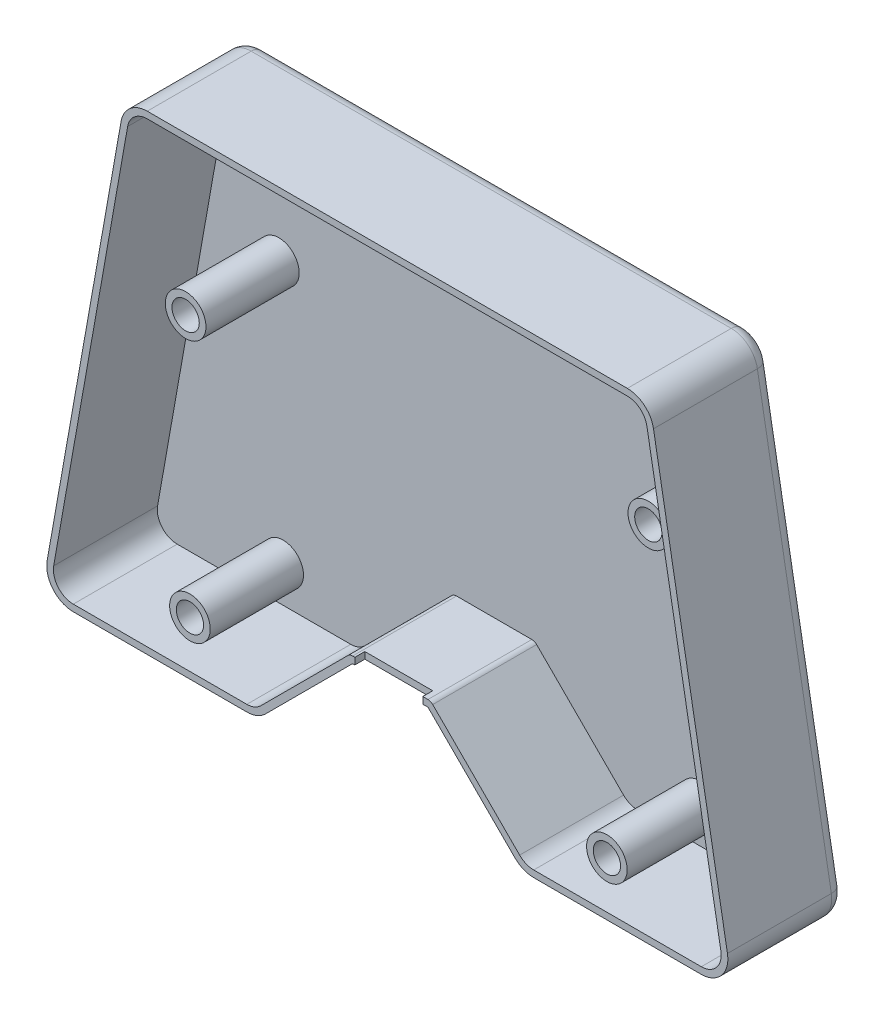
SolidWorks part; units mm, degrees
ref_plane "前视基准面" through (0, 0, 0) normal (0, 0, 1) x (1, 0, 0)
ref_plane "上视基准面" through (0, 0, 0) normal (0, 1, 0) x (1, 0, 0)
ref_plane "右视基准面" through (0, 0, 0) normal (1, 0, 0) x (0, 0, -1)
other "Configuration Table"
sketch "草图1" plane through (0, 0, 0) normal (0, 0, 1) x (1, 0, 0)
  line L94 (-18.737, -43.8075) -> (7.3198, -43.8075)
  line L95 (10.1392, -42.6396) -> (23.1917, -29.5872)
  line L96 (23.2007, -29.5835) -> (34.5123, -29.5835)
  line L97 (34.5213, -29.5872) -> (47.5737, -42.6396)
  line L98 (50.3932, -43.8075) -> (75.5524, -43.8075)
  line L99 (79.4785, -39.1247) -> (68.3761, 23.5504)
  line L100 (64.4499, 26.8422) -> (-7.6345, 26.8422)
  line L101 (-11.5607, 23.5504) -> (-22.6632, -39.1247)
  line L102 (-18.737, -43.8075) -> (7.3198, -43.8075)
  line L103 (10.1392, -42.6396) -> (23.1917, -29.5872)
  line L104 (23.2007, -29.5835) -> (34.5123, -29.5835)
  line L105 (34.5213, -29.5872) -> (47.5737, -42.6396)
  line L106 (50.3932, -43.8075) -> (75.5524, -43.8075)
  line L107 (79.4785, -39.1247) -> (68.3761, 23.5504)
  line L108 (64.4499, 26.8422) -> (-7.6345, 26.8422)
  line L109 (-11.5607, 23.5504) -> (-22.6632, -39.1247)
  arc A67 (-7.6345, 26.8422) -> (-11.5607, 23.5504) centre (-7.6345, 22.8549) ccw
  arc A68 (-22.6632, -39.1247) -> (-18.737, -43.8075) centre (-18.737, -39.8202) ccw
  arc A69 (7.3198, -43.8075) -> (10.1392, -42.6396) centre (7.3198, -39.8202) ccw
  arc A70 (23.2007, -29.5835) -> (23.1917, -29.5872) centre (23.2007, -29.5962) ccw
  arc A71 (34.5213, -29.5872) -> (34.5123, -29.5835) centre (34.5123, -29.5962) ccw
  arc A72 (47.5737, -42.6396) -> (50.3932, -43.8075) centre (50.3932, -39.8202) ccw
  arc A73 (75.5524, -43.8075) -> (79.4785, -39.1247) centre (75.5524, -39.8202) ccw
  arc A74 (68.3761, 23.5504) -> (64.4499, 26.8422) centre (64.4499, 22.8549) ccw
  arc A75 (-7.6345, 26.8422) -> (-11.5607, 23.5504) centre (-7.6345, 22.8549) ccw
  arc A76 (-22.6632, -39.1247) -> (-18.737, -43.8075) centre (-18.737, -39.8202) ccw
  arc A77 (7.3198, -43.8075) -> (10.1392, -42.6396) centre (7.3198, -39.8202) ccw
  arc A78 (23.2007, -29.5835) -> (23.1917, -29.5872) centre (23.2007, -29.5962) ccw
  arc A79 (34.5213, -29.5872) -> (34.5123, -29.5835) centre (34.5123, -29.5962) ccw
  arc A80 (47.5737, -42.6396) -> (50.3932, -43.8075) centre (50.3932, -39.8202) ccw
  arc A81 (75.5524, -43.8075) -> (79.4785, -39.1247) centre (75.5524, -39.8202) ccw
  arc A82 (68.3761, 23.5504) -> (64.4499, 26.8422) centre (64.4499, 22.8549) ccw
  point P0 (0, 0)
  dimension "D1" = 2
extrude "凸台-拉伸1" add sketch "草图1" along normal blind 2
sketch "草图4" plane through (0, 0, 2) normal (0, 0, 1) x (1, 0, 0)
  arc A9 (63.9498, 9.1069) -> (68.0498, 9.1069) centre (65.9998, 9.1069) ccw
  arc A10 (68.0498, 9.1069) -> (63.9498, 9.1069) centre (65.9998, 9.1069) ccw
  arc A11 (63.9498, 9.1069) -> (68.0498, 9.1069) centre (65.9998, 9.1069) ccw
  arc A12 (68.0498, 9.1069) -> (63.9498, 9.1069) centre (65.9998, 9.1069) ccw
  arc A22 (-0.7724, -37.3752) -> (-4.8724, -37.3752) centre (-2.8224, -37.3752) ccw
  arc A23 (-4.8724, -37.3752) -> (-0.7724, -37.3752) centre (-2.8224, -37.3752) ccw
  arc A24 (-0.7724, -37.3752) -> (-4.8724, -37.3752) centre (-2.8224, -37.3752) ccw
  arc A25 (-4.8724, -37.3752) -> (-0.7724, -37.3752) centre (-2.8224, -37.3752) ccw
  arc A29 (61.8277, -37.3752) -> (57.7277, -37.3752) centre (59.7777, -37.3752) ccw
  arc A30 (57.7277, -37.3752) -> (61.8277, -37.3752) centre (59.7777, -37.3752) ccw
  arc A31 (61.8277, -37.3752) -> (57.7277, -37.3752) centre (59.7777, -37.3752) ccw
  arc A32 (57.7277, -37.3752) -> (61.8277, -37.3752) centre (59.7777, -37.3752) ccw
  arc A34 (-5.8724, -37.3752) -> (0.2276, -37.3752) centre (-2.8224, -37.3752) ccw
  arc A35 (0.2276, -37.3752) -> (-5.8724, -37.3752) centre (-2.8224, -37.3752) ccw
  arc A36 (-1.4194, 1.6139) -> (-5.5194, 1.6139) centre (-3.4694, 1.6139) ccw
  arc A37 (-5.5194, 1.6139) -> (-1.4194, 1.6139) centre (-3.4694, 1.6139) ccw
  arc A38 (-1.4194, 1.6139) -> (-5.5194, 1.6139) centre (-3.4694, 1.6139) ccw
  arc A39 (-5.5194, 1.6139) -> (-1.4194, 1.6139) centre (-3.4694, 1.6139) ccw
  arc A40 (56.7277, -37.3752) -> (62.8277, -37.3752) centre (59.7777, -37.3752) ccw
  arc A41 (62.8277, -37.3752) -> (56.7277, -37.3752) centre (59.7777, -37.3752) ccw
  arc A42 (69.0498, 9.1069) -> (62.9498, 9.1069) centre (65.9998, 9.1069) ccw
  arc A43 (62.9498, 9.1069) -> (69.0498, 9.1069) centre (65.9998, 9.1069) ccw
  arc A44 (-6.5194, 1.6139) -> (-0.4194, 1.6139) centre (-3.4694, 1.6139) ccw
  arc A45 (-0.4194, 1.6139) -> (-6.5194, 1.6139) centre (-3.4694, 1.6139) ccw
  dimension "D1" = 0.4
  dimension "D2" = 0.4
  dimension "D3" = 0.4
  dimension "D4" = 0.4
  dimension "D5" = 1
extrude "凸台-拉伸2" add sketch "草图4" along normal blind 14
sketch "草图6" plane through (0, 0, 2) normal (0, 0, 1) x (1, 0, 0)
  line L0 (-10.576, 23.376) -> (-21.6785, -39.2991)
  line L1 (-18.737, -42.8075) -> (7.3198, -42.8075)
  line L2 (9.4321, -41.9325) -> (22.4845, -28.8801)
  line L3 (23.2007, -28.5835) -> (34.5123, -28.5835)
  line L4 (35.2284, -28.8801) -> (48.2808, -41.9325)
  line L5 (50.3932, -42.8075) -> (75.5524, -42.8075)
  line L6 (78.4939, -39.2991) -> (67.3914, 23.376)
  line L7 (64.4499, 25.8422) -> (-7.6345, 25.8422)
  line L8 (-11.5607, 23.5504) -> (-22.6632, -39.1247)
  line L9 (-18.737, -43.8075) -> (7.3198, -43.8075)
  line L10 (10.1392, -42.6396) -> (23.1917, -29.5872)
  line L11 (23.2007, -29.5835) -> (34.5123, -29.5835)
  line L12 (34.5213, -29.5872) -> (47.5737, -42.6396)
  line L13 (50.3932, -43.8075) -> (75.5524, -43.8075)
  line L14 (79.4785, -39.1247) -> (68.3761, 23.5504)
  line L15 (64.4499, 26.8422) -> (-7.6345, 26.8422)
  line L16 (-11.5607, 23.5504) -> (-22.6632, -39.1247)
  line L17 (-18.737, -43.8075) -> (7.3198, -43.8075)
  line L18 (10.1392, -42.6396) -> (23.1917, -29.5872)
  line L19 (23.2007, -29.5835) -> (34.5123, -29.5835)
  line L20 (34.5213, -29.5872) -> (47.5737, -42.6396)
  line L21 (50.3932, -43.8075) -> (75.5524, -43.8075)
  line L22 (79.4785, -39.1247) -> (68.3761, 23.5504)
  line L23 (64.4499, 26.8422) -> (-7.6345, 26.8422)
  arc A0 (-21.6785, -39.2991) -> (-18.737, -42.8075) centre (-18.737, -39.8202) ccw
  arc A1 (7.3198, -42.8075) -> (9.4321, -41.9325) centre (7.3198, -39.8202) ccw
  arc A2 (23.2007, -28.5835) -> (22.4845, -28.8801) centre (23.2007, -29.5962) ccw
  arc A3 (35.2284, -28.8801) -> (34.5123, -28.5835) centre (34.5123, -29.5962) ccw
  arc A4 (48.2808, -41.9325) -> (50.3932, -42.8075) centre (50.3932, -39.8202) ccw
  arc A5 (75.5524, -42.8075) -> (78.4939, -39.2991) centre (75.5524, -39.8202) ccw
  arc A6 (67.3914, 23.376) -> (64.4499, 25.8422) centre (64.4499, 22.8549) ccw
  arc A7 (-7.6345, 25.8422) -> (-10.576, 23.376) centre (-7.6345, 22.8549) ccw
  arc A8 (-7.6345, 26.8422) -> (-11.5607, 23.5504) centre (-7.6345, 22.8549) ccw
  arc A9 (-22.6632, -39.1247) -> (-18.737, -43.8075) centre (-18.737, -39.8202) ccw
  arc A10 (7.3198, -43.8075) -> (10.1392, -42.6396) centre (7.3198, -39.8202) ccw
  arc A11 (23.2007, -29.5835) -> (23.1917, -29.5872) centre (23.2007, -29.5962) ccw
  arc A12 (34.5213, -29.5872) -> (34.5123, -29.5835) centre (34.5123, -29.5962) ccw
  arc A13 (47.5737, -42.6396) -> (50.3932, -43.8075) centre (50.3932, -39.8202) ccw
  arc A14 (75.5524, -43.8075) -> (79.4785, -39.1247) centre (75.5524, -39.8202) ccw
  arc A15 (68.3761, 23.5504) -> (64.4499, 26.8422) centre (64.4499, 22.8549) ccw
  arc A16 (-7.6345, 26.8422) -> (-11.5607, 23.5504) centre (-7.6345, 22.8549) ccw
  arc A17 (-22.6632, -39.1247) -> (-18.737, -43.8075) centre (-18.737, -39.8202) ccw
  arc A18 (7.3198, -43.8075) -> (10.1392, -42.6396) centre (7.3198, -39.8202) ccw
  arc A19 (23.2007, -29.5835) -> (23.1917, -29.5872) centre (23.2007, -29.5962) ccw
  arc A20 (34.5213, -29.5872) -> (34.5123, -29.5835) centre (34.5123, -29.5962) ccw
  arc A21 (47.5737, -42.6396) -> (50.3932, -43.8075) centre (50.3932, -39.8202) ccw
  arc A22 (75.5524, -43.8075) -> (79.4785, -39.1247) centre (75.5524, -39.8202) ccw
  arc A23 (68.3761, 23.5504) -> (64.4499, 26.8422) centre (64.4499, 22.8549) ccw
  dimension "D1" = 0
  dimension "D2" = 1
extrude "凸台-拉伸3" add sketch "草图6" along normal up to surface (15.6001 mm away)
sketch "草图11" plane through (96.4894, -33.9679, 32.6745) normal (1, 0, 0) x (0, 0, -1)
  line L0 (32.6745, -9.8396) -> (23.8745, -9.8396)
  line L1 (15.0745, -9.8396) -> (32.6745, -9.8396) construction
  line L2 (23.8745, -9.8396) -> (32.6745, 29.1804)
  line L3 (32.6745, -5.1568) -> (32.6745, 57.5183) construction
  line L4 (32.6745, 29.1804) -> (32.6745, -9.8396)
  dimension "D1" = 40
fillet "圆角1" radius 2 16 edges at (78.6078, -42.382, 0) (62.9728, -43.8075, 0) (48.8673, -43.504, 0) (41.0475, -36.1134, 0) (34.5171, -29.5844, 0) (28.8565, -29.5835, 0) (23.1958, -29.5844, 0) (16.6655, -36.1134, 0) (8.8457, -43.504, 0) (-5.7086, -43.8075, 0) (-21.7925, -42.382, 0) (-17.1119, -7.7871, 0) (-10.1963, 25.9104, 0) (28.4077, 26.8422, 0) (67.0117, 25.9104, 0) (73.9273, -7.7871, 0)
sketch "草图12" plane through (0, -29.5835, 0) normal (0, -1, 0) x (1, 0, 0)
  line L0 (23.534, 16.1) -> (33.734, 16.1)
  line L1 (33.734, 16.1) -> (33.734, 18)
  line L2 (33.734, 18) -> (23.534, 18)
  line L3 (23.534, 18) -> (23.534, 16.1)
extrude "USB_TypeC_Lower_Half_Opening" cut sketch "草图12" against normal blind 4
